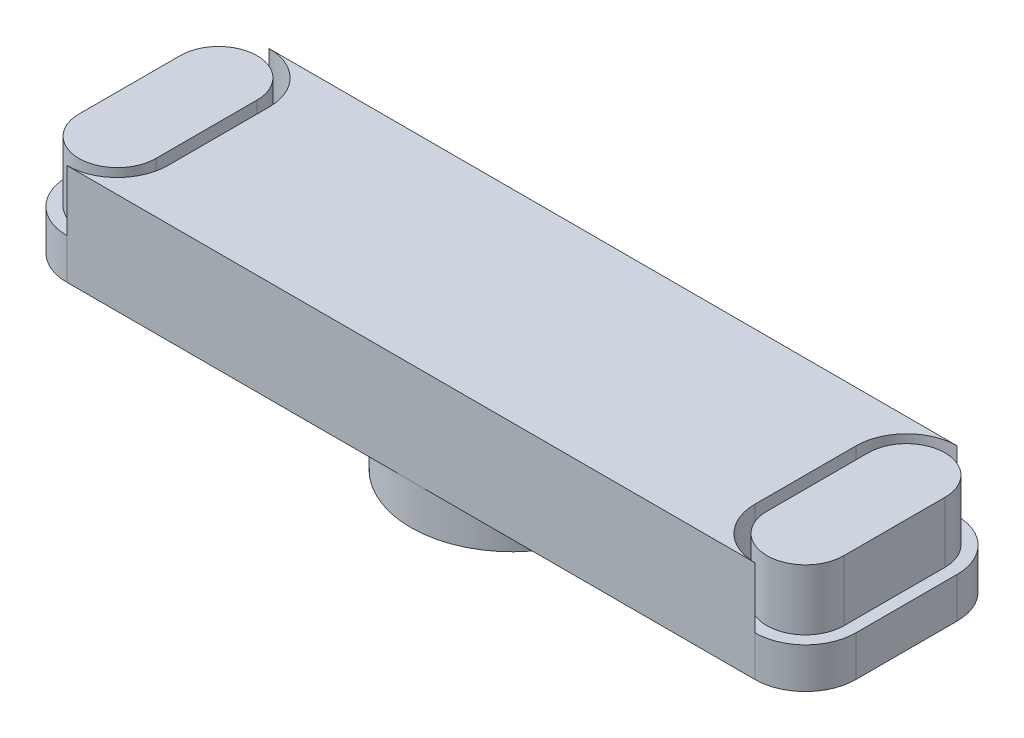
SolidWorks part; units mm, degrees
ref_plane "Plan de face" through (0, 0, 0) normal (0, 0, 1) x (1, 0, 0)
ref_plane "Plan de dessus" through (0, 0, 0) normal (0, 1, 0) x (1, 0, 0)
ref_plane "Plan de droite" through (0, 0, 0) normal (1, 0, 0) x (0, 0, -1)
sketch "Esquisse1" plane through (0, 0, 0) normal (0, 1, 0) x (1, 0, 0)
  line L1 (0, -5) -> (-19.5, -5)
  line L2 (0, -5) -> (19.5, -5)
  line L3 (0, 5) -> (19.5, 5)
  line L6 (-19.5, -5) -> (-19.5, 5)
  line L7 (-14.5, 0) -> (-19.5, 0)
  line L8 (-19.5, 5) -> (-14.5, 5)
  line L9 (-14.5, 5) -> (-14.5, -5)
  line L10 (-14.5, 5) -> (0, 5)
  line L11 (19.5, 0) -> (14.5, 0)
  line L12 (17, 0) -> (17, -5)
  line L13 (14.5, 2.5) -> (14.5, 5)
  line L14 (14.5, 5) -> (14.5, -5)
  line L15 (-17, 0) -> (-17, -5)
  line L16 (-17, -5) -> (-17, 5)
  line L17 (17, -5) -> (17, 5)
  line L18 (19.5, -5) -> (19.5, 5)
  line L19 (19.5, -2.5) -> (14.5, -2.5)
  line L21 (18.9, 2.5) -> (18.9, -2.5)
  line L22 (15.1, 2.5) -> (15.1, -2.5)
  line L23 (-14.5, -2.5) -> (-19.5, -2.5)
  line L24 (14.5, 0) -> (-14.5, 0)
  line L25 (-15.1, 2.5) -> (-15.1, -2.5)
  line L26 (-19.5, 2.5) -> (-14.5, 2.5)
  line L27 (14.5, 2.5) -> (19.5, 2.5)
  line L28 (-18.9, 2.5) -> (-18.9, -2.5)
  circle A0 centre (0, 0) radius 3.5
  circle A10 centre (0, 0) radius 5
  arc A23 (19.5, -2.5) -> (17, -5) centre (17, -2.5) cw
  arc A24 (17, -5) -> (14.5, -2.5) centre (17, -2.5) cw
  arc A25 (17, 5) -> (14.5, 2.5) centre (17, 2.5) ccw
  arc A26 (17, 5) -> (19.5, 2.5) centre (17, 2.5) cw
  arc A27 (-17, 5) -> (-19.5, 2.5) centre (-17, 2.5) ccw
  arc A28 (-14.5, 2.5) -> (-17, 5) centre (-17, 2.5) ccw
  arc A29 (-14.5, -2.5) -> (-17, -5) centre (-17, -2.5) cw
  arc A30 (-17, -5) -> (-19.5, -2.5) centre (-17, -2.5) cw
  arc A31 (15.1, 2.5) -> (18.9, 2.5) centre (17, 2.5) cw
  arc A32 (15.1, -2.5) -> (18.9, -2.5) centre (17, -2.5) ccw
  arc A33 (-18.9, 2.5) -> (-15.1, 2.5) centre (-17, 2.5) cw
  arc A34 (-18.9, -2.5) -> (-15.1, -2.5) centre (-17, -2.5) ccw
  dimension "D1" = 7
  dimension "D2" = 10
  dimension "D3" = 14.5
  dimension "D6" = 2.5
  dimension "D8" = 2.5
  dimension "D9" = 2.5
  dimension "D11" = 2.5
  dimension "D10" = 2.5
  dimension "D12" = 2.5
  dimension "D13" = 0.6
  dimension "D14" = 0.6
  dimension "D4" = 2.5
  dimension "D5" = 14.5
  dimension "D7" = 2.5
extrude "Boss.-Extru.2" add sketch "Esquisse1" against normal blind 5 contours L6 | L6 | L6 | L27 L21 L11 L18 | L17 A31 L27 A26 | L27 A31 L17 A25 | A25 L3 L13 | A31 L17 L27 | A31 L27 L17 | L27 L22 L11 L17 | L27 L17 L11 L21 | L21 L11 L12 L19 | L11 L22 L19 L12 | L19 A32 L17 | L17 A32 L19 | A32 L12 A23 L19 | L11 L21 L19 L18 | L27 L14 L11 L22 | L22 L11 L14 L19 | A32 L19 A24 L12 | L2 A24 L14 | A10 L2 L14 L24 | A10 L24 L14 L13 L3 | L24 A10 A0 | A10 L24 A0 | L24 A0 | L24 A0 | A10 L10 L9 L24 | A10 L24 L9 L1 | L9 A29 L1 | A34 L15 A29 L23 | A34 L23 A30 L15 | L23 A34 L16 | L16 A34 L23 | L25 L7 L15 L23 | L7 L28 L23 L15 | L28 L7 L6 L23 | L28 L26 L6 L7 | L26 A33 L16 A27 | L16 A33 L26 A28 | A28 L9 L8 | L26 L25 L7 L9 | L7 L25 L23 L9 | L26 L16 L7 L25 | A33 L16 L26 | A33 L26 L16 | L26 L28 L7 L16 region at (9.1546, 0, 2.6404) region at (-3.4565, 0, 3.4565) region at (-9.1546, 0, 2.6404) region at (-15.0584, 0, 4.4416) region at (15.0584, 0, 4.4416) region at (9.1546, 0, -2.6404) region at (4.25, 0, -0.1118) region at (-9.1546, 0, -2.6404) region at (-18.4092, 0, 3.9092) region at (-15.5908, 0, 3.9092) region at (-14.8, 0, 1.25) region at (15.5908, 0, 3.9092) region at (18.4092, 0, 3.9092) region at (14.8, 0, 1.25) region at (14.8, 0, -1.25) region at (0, 0, 1.4854) region at (0, 0, -1.4854) region at (-14.8, 0, -1.25) region at (-17.8064, 0, 3.3064) region at (-16.1936, 0, 3.3064) region at (-19.2, 0, 1.25) region at (-16.05, 0, 1.25) region at (16.1936, 0, 3.3064) region at (17.8064, 0, 3.3064) region at (19.2, 0, 1.25) region at (16.05, 0, 1.25) region at (16.05, 0, -1.25) region at (15.5908, 0, -3.9092) region at (15.0584, 0, -4.4416) region at (-15.0584, 0, -4.4416) region at (-16.05, 0, -1.25) region at (-15.5908, 0, -3.9092) region at (-17.95, 0, 1.25) region at (-19.2, 0, -1.25) region at (17.95, 0, 1.25) region at (19.2, 0, -1.25) region at (17.95, 0, -1.25) region at (16.1936, 0, -3.3064) region at (18.4092, 0, -3.9092) region at (-18.4092, 0, -3.9092) region at (-17.95, 0, -1.25) region at (-16.1936, 0, -3.3064) region at (17.8064, 0, -3.3064) region at (-17.8064, 0, -3.3064)
extrude "Boss.-Extru.7" add sketch "Esquisse1<9>" against normal blind 7 contours L24 A10 A0 | A10 L24 A0 region at (-3.4565, 0, 3.4565) region at (4.25, 0, -0.1118)
sketch "Esquisse1<9>" plane through (0, 0, 0) normal (0, 1, 0) x (1, 0, 0) same geometry as "Esquisse1"
extrude "Enlèv. mat.-Extru.3" cut sketch "Esquisse1<13>" against normal blind 3 contours L27 A31 L17 A25 | L17 A31 L27 A26 | L27 L21 L11 L18 | L11 L21 L19 L18 | A32 L12 A23 L19 | A32 L19 A24 L12 | L22 L11 L14 L19 | L27 L14 L11 L22 region at (15.5908, 0, 3.9092) region at (18.4092, 0, 3.9092) region at (14.8, 0, 1.25) region at (14.8, 0, -1.25) region at (19.2, 0, 1.25) region at (15.5908, 0, -3.9092) region at (19.2, 0, -1.25) region at (18.4092, 0, -3.9092)
sketch "Esquisse1<13>" plane through (0, 0, 0) normal (0, 1, 0) x (1, 0, 0) same geometry as "Esquisse1"
extrude "Enlèv. mat.-Extru.4" cut sketch "Esquisse1<16>" against normal blind 3 contours A34 L23 A30 L15 | L28 L7 L6 L23 | L28 L26 L6 L7 | L26 A33 L16 A27 | L16 A33 L26 A28 | L26 L25 L7 L9 | L7 L25 L23 L9 | A34 L15 A29 L23 region at (-18.4092, 0, 3.9092) region at (-15.5908, 0, 3.9092) region at (-14.8, 0, 1.25) region at (-14.8, 0, -1.25) region at (-19.2, 0, 1.25) region at (-15.5908, 0, -3.9092) region at (-19.2, 0, -1.25) region at (-18.4092, 0, -3.9092)
sketch "Esquisse1<16>" plane through (0, 0, 0) normal (0, 1, 0) x (1, 0, 0) same geometry as "Esquisse1"
